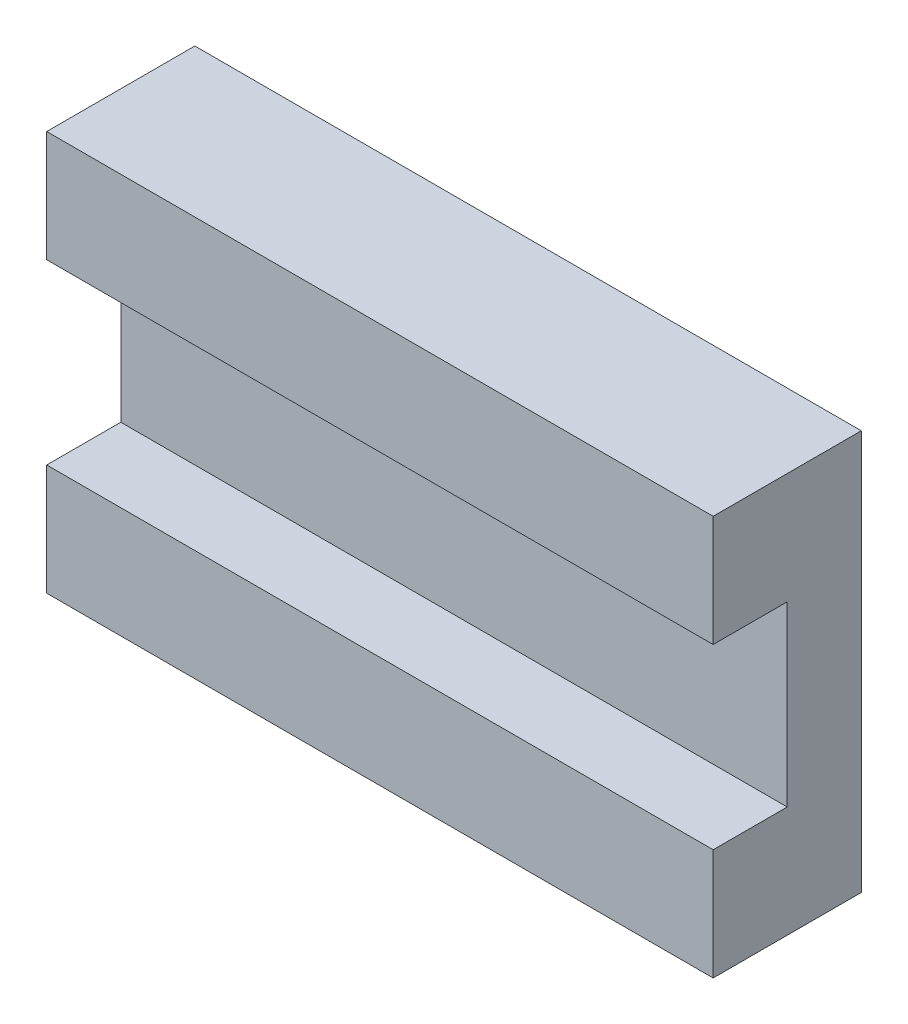
SolidWorks part; units mm, degrees
ref_plane "Front Plane" through (0, 0, 0) normal (0, 0, 1) x (1, 0, 0)
ref_plane "Top Plane" through (0, 0, 0) normal (0, 1, 0) x (1, 0, 0)
ref_plane "Right Plane" through (0, 0, 0) normal (1, 0, 0) x (0, 0, -1)
sketch "Sketch1" plane through (0, 0, 0) normal (0, 0, 1) x (1, 0, 0)
  line L1 (-22.5, -13.5) -> (22.5, -13.5)
  line L2 (-22.5, -13.5) -> (-22.5, 13.5)
  line L3 (-22.5, 13.5) -> (22.5, 13.5)
  line L4 (22.5, -13.5) -> (22.5, 13.5)
  line L5 (-22.5, -13.5) -> (22.5, 13.5) construction
  line L6 (-22.5, 13.5) -> (22.5, -13.5) construction
  line L7 (-10, -10) -> (10, -10) construction
  line L8 (-10, -10) -> (-10, 10) construction
  line L9 (-10, 10) -> (10, 10) construction
  line L10 (10, -10) -> (10, 10) construction
  line L11 (-10, -10) -> (10, 10) construction
  line L12 (-10, 10) -> (10, -10) construction
  circle A0 centre (-10, 10) radius 1.5
  circle A1 centre (10, 10) radius 1.5
  circle A2 centre (10, -10) radius 1.5
  circle A3 centre (-10, -10) radius 1.5
  point P0 (0, 0)
  point P6 (0, 0)
  dimension "D1" = 45
  dimension "D2" = 27
  dimension "D3" = 20
  dimension "D4" = 20
extrude "Boss-Extrude1" add sketch "Sketch1" along normal blind 10 contours A0 | A1 | A2 | A3 | L1 L4 L3 L2 A3 A2 A1 A0 region at (0, 0, 0) region at (-10, 10, 0) region at (10, 10, 0) region at (10, -10, 0) region at (-10, -10, 0)
extrude "Cut-Extrude1" cut sketch "Sketch1<3>" along normal blind 5 contours A0 | A1 | A2 | A3 region at (-10, 10, 0) region at (10, 10, 0) region at (10, -10, 0) region at (-10, -10, 0)
sketch "Sketch1<3>" plane through (0, 0, 0) normal (0, 0, 1) x (1, 0, 0) same geometry as "Sketch1"
sketch "Sketch2" plane through (0, 0, 10) normal (0, 0, 1) x (1, 0, 0)
  line L0 (22.5, -13.5) -> (22.5, 13.5) construction
  line L1 (-22.5, 6) -> (22.5, 6)
  line L2 (-22.5, 6) -> (-22.5, -6)
  line L3 (-22.5, -6) -> (22.5, -6)
  line L4 (22.5, 6) -> (22.5, -6)
  line L5 (-22.5, 6) -> (22.5, -6) construction
  line L6 (-22.5, -6) -> (22.5, 6) construction
  point P0 (0, 0)
  dimension "D1" = 12
extrude "Cut-Extrude2" cut sketch "Sketch2" against normal blind 5
